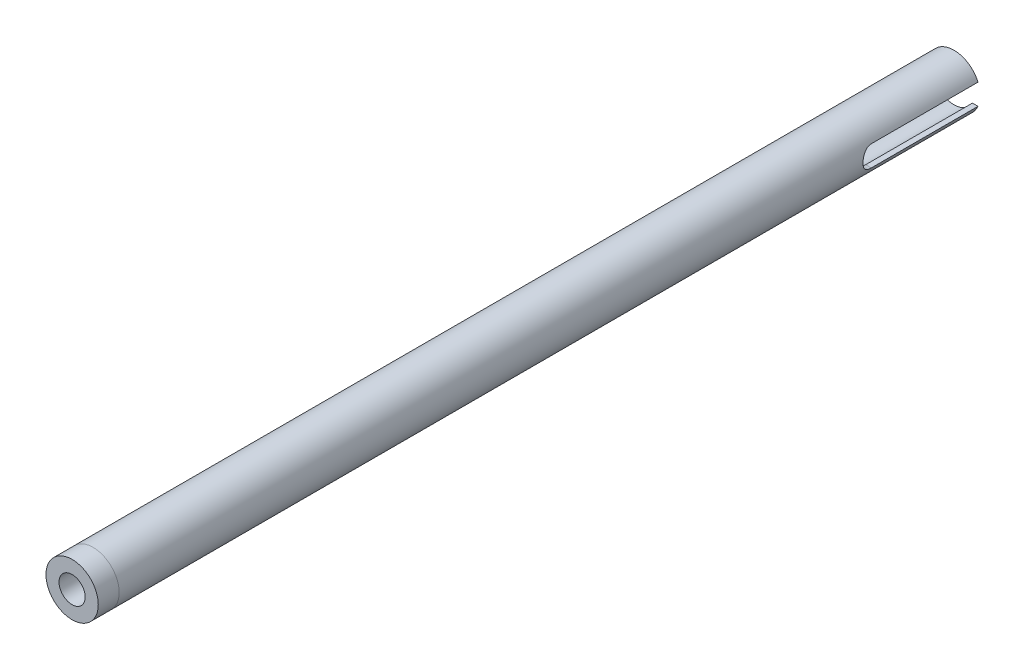
SolidWorks part; units mm, degrees
material "AISI 4130 Steel, annealed at 865C"
ref_plane "Front Plane" through (0, 0, 0) normal (0, 0, 1) x (1, 0, 0)
ref_plane "Top Plane" through (0, 0, 0) normal (0, 1, 0) x (1, 0, 0)
ref_plane "Right Plane" through (0, 0, 0) normal (1, 0, 0) x (0, 0, -1)
sketch "Axis" plane through (0, 0, 0) normal (0, 1, 0) x (1, 0, 0)
  line L0 (0, 0) -> (0, 267.6401) construction
  line L1 (0, 0) -> (0, -28.575) construction
  line L2 (0, 267.6401) -> (-7.9375, 267.6401) construction
  line L4 (0, 291.0683) -> (-10.3188, 260.6116) construction
  dimension "D1" = 28.575
  dimension "D2" = 7.9375
sketch "Sketch1" plane through (0, 0, 0) normal (0, 0, 1) x (1, 0, 0)
  line L0 (-7.9375, 0) -> (7.9375, 0) construction
  line L1 (-7.2748, 3.175) -> (7.2748, 3.175)
  line L2 (-7.2748, -3.175) -> (7.2748, -3.175)
  circle A0 centre (0, 0) radius 7.9375
  circle A1 centre (0, 0) radius 6.4135
  circle A2 centre (0, 0) radius 3.9688
  dimension "D1" = 15.875
  dimension "D3" = 7.9375
  dimension "D2" = 1.524
  dimension "D4" = 6.35
extrude "Threaded insert 1-1" add sketch "Sketch1" against normal blind 6.35 contours A2 L1 A1 | A1 L1 A0 | A2 L0 A1 L1 | A1 L0 A0 L1 | L0 A1 L2 A0 | L0 A2 L2 A1 | A2 L2 A1 | A1 L2 A0 | L0 A1 L2 A2 | L0 A0 L2 A1 | A0 L0 A1 L1 | A1 L0 A2 L1 region at (4.7887, 1.6543, 0) region at (4.7887, -1.6543, 0) region at (6.9234, 1.6163, 0) region at (6.9234, -1.6163, 0) region at (-4.7887, -1.6543, 0) region at (-4.7887, 1.6543, 0) region at (0, 4.6159, 0) region at (0, -4.6159, 0) region at (0, 6.5666, 0) region at (6.4237, -3.3281, 0) region at (-6.9234, -1.6163, 0) region at (-6.9234, 1.6163, 0)
extrude "Threaded insert 1-2" add sketch "Sketch1<3>" against normal blind 9.525 from surface contours A2 L1 A1 | A2 L0 A1 L1 | L0 A2 L2 A1 | A2 L2 A1 | L0 A1 L2 A2 | A1 L0 A2 L1 region at (4.7887, 1.6543, 0) region at (4.7887, -1.6543, 0) region at (-4.7887, -1.6543, 0) region at (-4.7887, 1.6543, 0) region at (0, 4.6159, 0) region at (0, -4.6159, 0) starting at face at (7.9375, 0, -6.35)
sketch "Sketch1<3>" plane through (0, 0, 0) normal (0, 0, 1) x (1, 0, 0) same geometry as "Sketch1"
extrude "A-arm tube" add sketch "Sketch1<4>" against normal up to vertex (267.6401 mm away) from surface separate body contours A1 L1 A0 | A1 L0 A0 L1 | L0 A1 L2 A0 | A1 L2 A0 | L0 A0 L2 A1 | A0 L0 A1 L1 region at (6.9234, 1.6163, 0) region at (6.9234, -1.6163, 0) region at (0, 6.5666, 0) region at (6.4237, -3.3281, 0) region at (-6.9234, -1.6163, 0) region at (-6.9234, 1.6163, 0) up to point (0, 0, -267.6401) starting at face at (6.4135, 0, -6.35)
sketch "Sketch1<4>" plane through (0, 0, 0) normal (0, 0, 1) x (1, 0, 0) same geometry as "Sketch1"
extrude "Apex slot" cut sketch "Sketch1<5>" along normal blind 35.56 from surface contours A0 L0 A1 L1 | L0 A0 L2 A1 | A1 L0 A0 L1 | L0 A1 L2 A0 region at (6.9234, 1.6163, 0) region at (6.9234, -1.6163, 0) region at (-6.9234, -1.6163, 0) region at (-6.9234, 1.6163, 0) starting at face at (6.4135, 0, -267.6401)
sketch "Sketch1<5>" plane through (0, 0, 0) normal (0, 0, 1) x (1, 0, 0) same geometry as "Sketch1"
fillet "Fillet1" radius 3.175 4 edges at (-6.4237, 3.175, -232.0801) (-6.4237, -3.175, -232.0801) (6.4237, -3.175, -232.0801) (6.4237, 3.175, -232.0801)
equation "\"tube diameter\"= 5 / 8"
equation "\"tube thickness\"= .06"
equation "\"apex thickness\"= .25"
equation "\"tube slot\"= 1.4"
equation "\"D1@Sketch1\"=\"tube diameter\""
equation "\"D2@Sketch1\"=\"tube thickness\""
equation "\"threaded insert hole\"= .3125"
equation "\"D3@Sketch1\"=\"threaded insert hole\""
equation "\"D4@Sketch1\"=\"apex thickness\""
equation "\"D1@Apex slot\" = \"tube slot\""
equation "\"D1@Fillet1\"=\"apex thickness\"/2"
